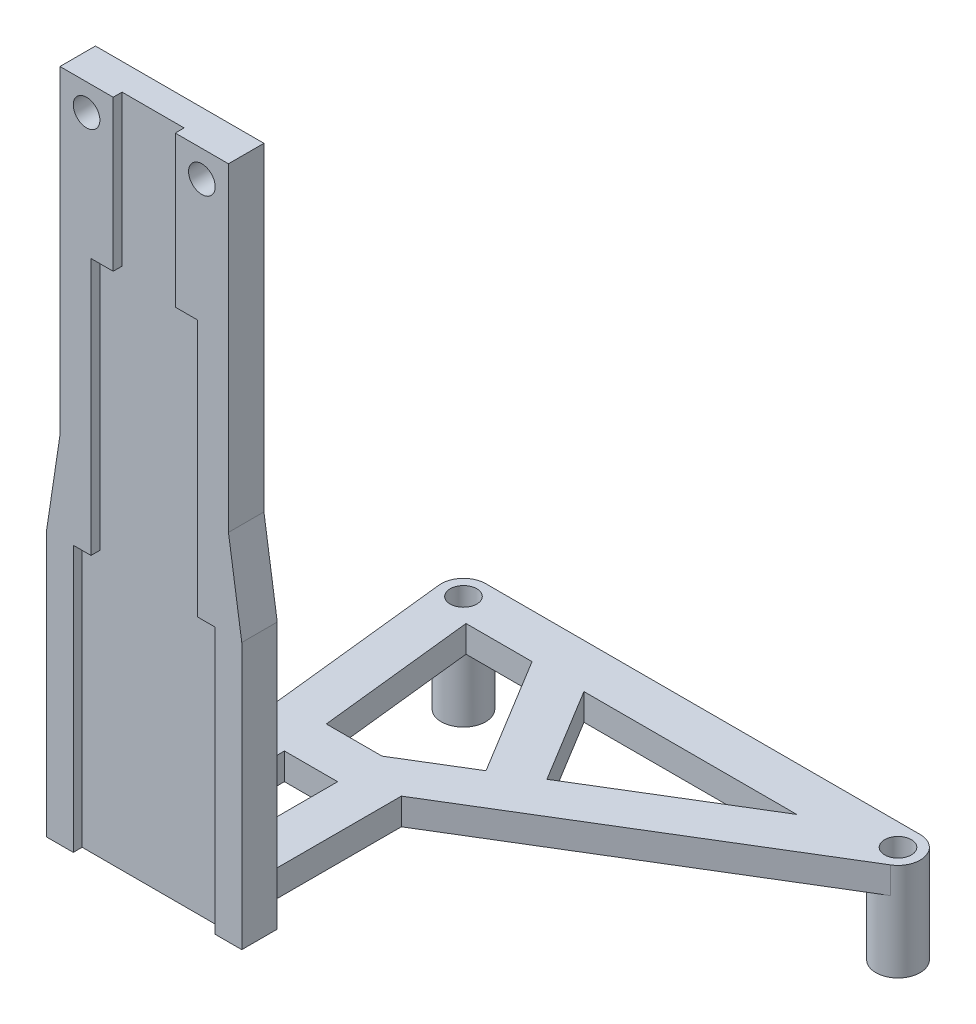
SolidWorks part; units mm, degrees
ref_plane "Front Plane" through (0, 0, 0) normal (0, 0, 1) x (1, 0, 0)
ref_plane "Top Plane" through (0, 0, 0) normal (0, 1, 0) x (1, 0, 0)
ref_plane "Right Plane" through (0, 0, 0) normal (1, 0, 0) x (0, 0, -1)
sketch "Esquisse1" plane through (0, 0, 0) normal (0, 1, 0) x (1, 0, 0)
  line L0 (-24.5, 0) -> (24.5, 0) construction
  circle A0 centre (-24.5, 0) radius 1.5
  circle A1 centre (24.5, 0) radius 1.5
  circle A2 centre (-24.5, 0) radius 2.5
  circle A3 centre (24.5, 0) radius 2.5
  dimension "D1" = 3
  dimension "D2" = 3
  dimension "D3" = 5
  dimension "D4" = 5
  dimension "D5" = 49
extrude "Boss.-Extru.1" add sketch "Esquisse1" along normal blind 8
sketch "Esquisse2" plane through (0, 8, 0) normal (0, 1, 0) x (1, 0, 0)
  line L0 (-24.5, -43) -> (-8.5, -43) construction
  line L1 (-24.5, 0) -> (-24.5, -43) construction
  line L2 (-24.5, 2.5) -> (24.5, 2.5)
  line L3 (-8.5, -43) -> (-8.5, -23)
  line L4 (-8.5, -23) -> (25.7992, -2.1359)
  line L5 (-24.5, -43) -> (-24.5, -23)
  line L6 (-24.5, -23) -> (-26.9852, -0.2717)
  line L7 (-24.5, -23) -> (-8.5, -23) construction
  line L8 (-24.5, -43) -> (-8.5, -43)
  circle A0 centre (-24.5, 0) radius 2.5 construction
  circle A1 centre (-24.5, 0) radius 1.5 construction
  circle A2 centre (24.5, 0) radius 1.5 construction
  circle A3 centre (-24.5, 0) radius 1.5
  circle A4 centre (24.5, 0) radius 1.5
  circle A5 centre (24.5, 0) radius 2.5 construction
  arc A6 (25.7992, -2.1359) -> (24.5, 2.5) centre (24.5, 0) ccw
  arc A7 (-24.5, 2.5) -> (-26.9852, -0.2717) centre (-24.5, 0) ccw
  point P14 (-26.9399, -0.5449)
  point P20 (-22.5, 1.5)
  point P21 (26.3615, -1.6688)
  point P24 (25.4085, 2.3291)
  dimension "D2" = 16
  dimension "D1" = 43
  dimension "D3" = 20
extrude "Boss.-Extru.2" add sketch "Esquisse2" along normal blind 3
sketch "Esquisse3" plane through (0, 11, 0) normal (0, 1, 0) x (1, 0, 0)
  line L0 (-6.2062, -15.7523) -> (-14.2676, -2.5)
  line L1 (-8.4152, -2.5) -> (-1.9345, -13.1538)
  line L2 (-5.1748, -7.8269) -> (-9.4466, -10.4254) construction
  line L3 (-7.3107, -9.1262) -> (-4.0704, -14.4531) construction
  line L4 (-14.2676, -2.5) -> (-21.7117, -2.5)
  line L5 (-1.9345, -13.1538) -> (15.5797, -2.5)
  line L6 (-13.5, -20.1891) -> (-19.7776, -20.1891)
  line L7 (-13.5, -25.1891) -> (-19.5, -25.1891)
  line L12 (-19.5, -38) -> (-13.5, -38)
  line L13 (-13.5, -38) -> (-13.5, -20.1891)
  line L14 (-13.5, -20.1891) -> (15.5797, -2.5)
  line L15 (15.5797, -2.5) -> (-21.7117, -2.5)
  line L16 (-21.7117, -2.5) -> (-19.5, -22.7275)
  line L17 (-19.5, -22.7275) -> (-19.5, -38)
  line L18 (-19.5, -38) -> (-13.5, -38)
  line L19 (-13.5, -38) -> (-13.5, -25.1891)
  line L20 (-13.5, -20.1891) -> (-6.2062, -15.7523)
  line L21 (15.5797, -2.5) -> (-8.4152, -2.5)
  line L22 (-21.7117, -2.5) -> (-19.7776, -20.1891)
  line L23 (-19.5, -25.1891) -> (-19.5, -38)
  dimension "D2" = 23
  dimension "D3" = 5
  dimension "D4" = 5
  dimension "D1" = 5
extrude "Enlèv. mat.-Extru.1" cut sketch "Esquisse3" against normal blind 3
sketch "Esquisse4" plane through (0, 11, 0) normal (0, 1, 0) x (1, 0, 0)
  line L0 (-24.5, -44) -> (-27.5, -44)
  line L1 (-27.5, -44) -> (-27.5, -40)
  line L2 (-27.5, -40) -> (-24.5, -40)
  line L3 (-24.5, -23) -> (-24.5, -43) construction
  line L4 (-24.5, -40) -> (-8.5, -40)
  line L5 (-8.5, -43) -> (-8.5, -23) construction
  line L6 (-8.5, -40) -> (-5.5, -40)
  line L7 (-5.5, -40) -> (-5.5, -44)
  line L8 (-5.5, -44) -> (-8.5, -44)
  line L9 (-8.5, -44) -> (-8.5, -43)
  line L10 (-8.5, -43) -> (-24.5, -43)
  line L11 (-24.5, -43) -> (-24.5, -44)
  point P16 (-22.961, -46)
  dimension "D1" = 3
  dimension "D2" = 1
  dimension "D3" = 3
extrude "Boss.-Extru.3" add sketch "Esquisse4" along normal blind 27 and the other way up to surface other way up to face at (-16.5, 8, 31.5945)
sketch "Esquisse5" plane through (0, 38, 0) normal (0, 1, 0) x (1, 0, 0)
  line L0 (-26, -44) -> (-22.5, -44)
  line L1 (-22.5, -44) -> (-22.5, -43)
  line L2 (-24.5, -43) -> (-8.5, -43) construction
  line L3 (-22.5, -43) -> (-10.5, -43)
  line L4 (-10.5, -43) -> (-10.5, -44)
  line L5 (-10.5, -44) -> (-7, -44)
  line L6 (-26, -44) -> (-26, -40)
  line L7 (-5.5, -40) -> (-27.5, -40) construction
  line L8 (-26, -40) -> (-7, -40)
  line L9 (-7, -40) -> (-7, -44)
  line L10 (-8.5, -44) -> (-5.5, -44) construction
  line L11 (-27.5, -44) -> (-24.5, -44) construction
  point P2 (-7, -46)
  point P9 (-26, -46)
  point P14 (-7.6162, -46)
  dimension "D1" = 12
extrude "Boss.-Extru.5" add sketch "Esquisse5" along normal blind 29
sketch "Esquisse6" plane through (0, 67, 0) normal (0, 1, 0) x (1, 0, 0)
  line L0 (-20, -44) -> (-20, -43)
  line L1 (-22.5, -43) -> (-10.5, -43) construction
  line L2 (-20, -43) -> (-13, -43)
  line L3 (-13, -43) -> (-13, -44)
  line L4 (-13, -44) -> (-7, -44)
  line L5 (-7, -44) -> (-7, -40)
  line L6 (-7, -40) -> (-26, -40) construction
  line L7 (-7, -40) -> (-26, -40)
  line L8 (-26, -40) -> (-26, -44)
  line L9 (-26, -44) -> (-20, -44)
  point P14 (-8.75, -46)
  point P15 (-7, -44)
  point P16 (-26, -44)
  dimension "D1" = 7
extrude "Boss.-Extru.6" add sketch "Esquisse6" along normal blind 17
sketch "Esquisse7" plane through (0, 0, 44) normal (0, 0, 1) x (1, 0, 0)
  line L0 (-23, 84) -> (-23, 81) construction
  line L1 (-26, 84) -> (-20, 84) construction
  line L2 (-23, 81) -> (-10, 81) construction
  line L3 (-10, 81) -> (-10, 84) construction
  line L4 (-13, 84) -> (-7, 84) construction
  line L5 (-23, 81) -> (-26, 81) construction
  line L6 (-26, 84) -> (-26, 38) construction
  circle A0 centre (-23, 81) radius 1.5
  circle A1 centre (-10, 81) radius 1.5
  dimension "D1" = 3
extrude "Enlèv. mat.-Extru.2" cut sketch "Esquisse7" against normal through all
chamfer "Chanfrein1" distance 1.5 distance2 10 2 edges at (-26, 38, 42) (-7, 38, 42) first distance on face at (-26.75, 38, 42) first distance on face at (-6.25, 38, 42)
